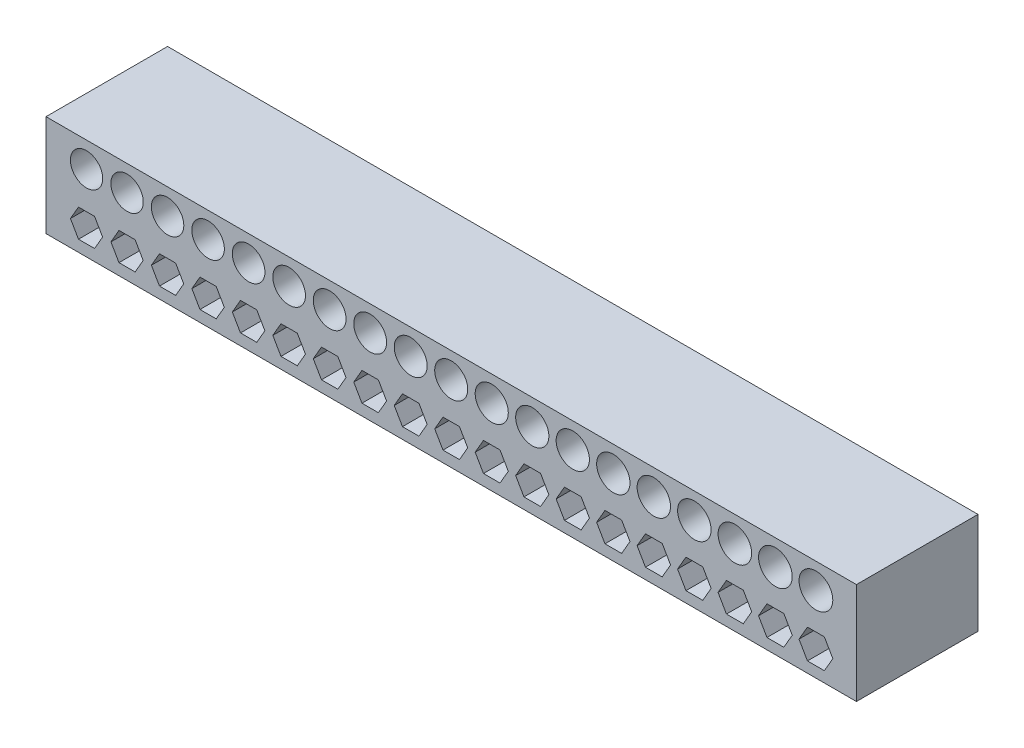
SolidWorks part; units mm, degrees
ref_plane "Front Plane" through (0, 0, 0) normal (0, 0, 1) x (1, 0, 0)
ref_plane "Top Plane" through (0, 0, 0) normal (0, 1, 0) x (1, 0, 0)
ref_plane "Right Plane" through (0, 0, 0) normal (1, 0, 0) x (0, 0, -1)
sketch "Sketch1" plane through (0, 0, 0) normal (0, 0, 1) x (1, 0, 0)
  line L0 (-93.9567, 6.25) -> (-91.9783, 9.6766) construction
  line L1 (-100, -12.5) -> (100, -12.5)
  line L2 (-100, -12.5) -> (-100, 12.5)
  line L3 (-100, 12.5) -> (100, 12.5)
  line L4 (100, -12.5) -> (100, 12.5)
  line L5 (-100, -12.5) -> (100, 12.5) construction
  line L6 (0, 12.5) -> (0, 0)
  line L7 (-91.9783, 9.6766) -> (-88.0217, 9.6766) construction
  line L8 (-88.0217, 9.6766) -> (-86.0433, 6.25) construction
  line L9 (-88.0217, 2.8234) -> (-91.9783, 2.8234) construction
  line L10 (-86.0433, 6.25) -> (-88.0217, 2.8234) construction
  line L11 (-91.9783, 2.8234) -> (-93.9567, 6.25) construction
  line L12 (-93.9567, 6.25) -> (-91.9783, 9.6766) construction
  line L13 (-91.9783, 9.6766) -> (-88.0217, 9.6766) construction
  line L14 (-88.0217, 9.6766) -> (-86.0433, 6.25) construction
  line L15 (-88.0217, 2.8234) -> (-91.9783, 2.8234) construction
  line L16 (-86.0433, 6.25) -> (-88.0217, 2.8234) construction
  line L17 (-91.9783, 2.8234) -> (-93.9567, 6.25) construction
  line L18 (0, 0) -> (0, -12.5)
  line L25 (-3.9567, -6.25) -> (-1.9783, -2.8234) construction
  line L26 (-13.9567, -6.25) -> (-11.9783, -2.8234) construction
  line L27 (-1.9783, -2.8234) -> (1.9783, -2.8234) construction
  line L28 (1.9783, -2.8234) -> (3.9567, -6.25) construction
  line L29 (1.9783, -9.6766) -> (-1.9783, -9.6766) construction
  line L30 (3.9567, -6.25) -> (1.9783, -9.6766) construction
  line L31 (-1.9783, -9.6766) -> (-3.9567, -6.25) construction
  line L32 (-1.9783, -9.6766) -> (1.9783, -2.8234) construction
  line L33 (-3.9567, -6.25) -> (3.9567, -6.25) construction
  line L34 (1.9783, -9.6766) -> (-1.9783, -2.8234) construction
  line L35 (-11.9783, -2.8234) -> (-8.0217, -2.8234) construction
  line L36 (-8.0217, -2.8234) -> (-6.0433, -6.25) construction
  line L37 (-6.0433, -6.25) -> (-8.0217, -9.6766) construction
  line L38 (-11.9783, -9.6766) -> (-13.9567, -6.25) construction
  line L39 (-8.0217, -9.6766) -> (-11.9783, -9.6766) construction
  line L40 (-23.9567, -6.25) -> (-21.9783, -2.8234) construction
  line L41 (-21.9783, -2.8234) -> (-18.0217, -2.8234) construction
  line L42 (-18.0217, -2.8234) -> (-16.0433, -6.25) construction
  line L43 (-16.0433, -6.25) -> (-18.0217, -9.6766) construction
  line L44 (-21.9783, -9.6766) -> (-23.9567, -6.25) construction
  line L45 (-18.0217, -9.6766) -> (-21.9783, -9.6766) construction
  line L46 (-33.9567, -6.25) -> (-31.9783, -2.8234) construction
  line L47 (-31.9783, -2.8234) -> (-28.0217, -2.8234) construction
  line L48 (-28.0217, -2.8234) -> (-26.0433, -6.25) construction
  line L49 (-26.0433, -6.25) -> (-28.0217, -9.6766) construction
  line L50 (-31.9783, -9.6766) -> (-33.9567, -6.25) construction
  line L51 (-28.0217, -9.6766) -> (-31.9783, -9.6766) construction
  line L52 (-43.9567, -6.25) -> (-41.9783, -2.8234) construction
  line L53 (-41.9783, -2.8234) -> (-38.0217, -2.8234) construction
  line L54 (-38.0217, -2.8234) -> (-36.0433, -6.25) construction
  line L55 (-36.0433, -6.25) -> (-38.0217, -9.6766) construction
  line L56 (-41.9783, -9.6766) -> (-43.9567, -6.25) construction
  line L57 (-38.0217, -9.6766) -> (-41.9783, -9.6766) construction
  line L58 (-53.9567, -6.25) -> (-51.9783, -2.8234) construction
  line L59 (-51.9783, -2.8234) -> (-48.0217, -2.8234) construction
  line L60 (-48.0217, -2.8234) -> (-46.0433, -6.25) construction
  line L61 (-46.0433, -6.25) -> (-48.0217, -9.6766) construction
  line L62 (-51.9783, -9.6766) -> (-53.9567, -6.25) construction
  line L63 (-48.0217, -9.6766) -> (-51.9783, -9.6766) construction
  line L64 (-63.9567, -6.25) -> (-61.9783, -2.8234) construction
  line L65 (-61.9783, -2.8234) -> (-58.0217, -2.8234) construction
  line L66 (-58.0217, -2.8234) -> (-56.0433, -6.25) construction
  line L67 (-56.0433, -6.25) -> (-58.0217, -9.6766) construction
  line L68 (-61.9783, -9.6766) -> (-63.9567, -6.25) construction
  line L69 (-58.0217, -9.6766) -> (-61.9783, -9.6766) construction
  line L70 (-73.9567, -6.25) -> (-71.9783, -2.8234) construction
  line L71 (-71.9783, -2.8234) -> (-68.0217, -2.8234) construction
  line L72 (-68.0217, -2.8234) -> (-66.0433, -6.25) construction
  line L73 (-66.0433, -6.25) -> (-68.0217, -9.6766) construction
  line L74 (-71.9783, -9.6766) -> (-73.9567, -6.25) construction
  line L75 (-68.0217, -9.6766) -> (-71.9783, -9.6766) construction
  line L76 (-83.9567, -6.25) -> (-81.9783, -2.8234) construction
  line L77 (-81.9783, -2.8234) -> (-78.0217, -2.8234) construction
  line L78 (-78.0217, -2.8234) -> (-76.0433, -6.25) construction
  line L79 (-76.0433, -6.25) -> (-78.0217, -9.6766) construction
  line L80 (-81.9783, -9.6766) -> (-83.9567, -6.25) construction
  line L81 (-78.0217, -9.6766) -> (-81.9783, -9.6766) construction
  line L82 (-93.9567, -6.25) -> (-91.9783, -2.8234) construction
  line L83 (-91.9783, -2.8234) -> (-88.0217, -2.8234) construction
  line L84 (-88.0217, -2.8234) -> (-86.0433, -6.25) construction
  line L85 (-86.0433, -6.25) -> (-88.0217, -9.6766) construction
  line L86 (-91.9783, -9.6766) -> (-93.9567, -6.25) construction
  line L87 (-88.0217, -9.6766) -> (-91.9783, -9.6766) construction
  line L88 (-3.9567, -6.25) -> (-13.9567, -6.25) construction
  line L89 (-91.9841, -2.8134) -> (-88.0159, -2.8134)
  line L90 (-88.0159, -2.8134) -> (-86.0318, -6.25)
  line L91 (-86.0318, -6.25) -> (-88.0159, -9.6866)
  line L92 (-88.0159, -9.6866) -> (-91.9841, -9.6866)
  line L93 (-91.9841, -9.6866) -> (-93.9682, -6.25)
  line L94 (-93.9682, -6.25) -> (-91.9841, -2.8134)
  line L95 (-81.9899, -2.8034) -> (-78.0101, -2.8034)
  line L96 (-78.0101, -2.8034) -> (-76.0202, -6.25)
  line L97 (-76.0202, -6.25) -> (-78.0101, -9.6966)
  line L98 (-78.0101, -9.6966) -> (-81.9899, -9.6966)
  line L99 (-81.9899, -9.6966) -> (-83.9798, -6.25)
  line L100 (-83.9798, -6.25) -> (-81.9899, -2.8034)
  line L101 (-71.9957, -2.7934) -> (-68.0043, -2.7934)
  line L102 (-68.0043, -2.7934) -> (-66.0087, -6.25)
  line L103 (-66.0087, -6.25) -> (-68.0043, -9.7066)
  line L104 (-68.0043, -9.7066) -> (-71.9957, -9.7066)
  line L105 (-71.9957, -9.7066) -> (-73.9913, -6.25)
  line L106 (-73.9913, -6.25) -> (-71.9957, -2.7934)
  line L107 (-62.0014, -2.7834) -> (-57.9986, -2.7834)
  line L108 (-57.9986, -2.7834) -> (-55.9971, -6.25)
  line L109 (-55.9971, -6.25) -> (-57.9986, -9.7166)
  line L110 (-57.9986, -9.7166) -> (-62.0014, -9.7166)
  line L111 (-62.0014, -9.7166) -> (-64.0029, -6.25)
  line L112 (-64.0029, -6.25) -> (-62.0014, -2.7834)
  line L113 (-52.0072, -2.7734) -> (-47.9928, -2.7734)
  line L114 (-47.9928, -2.7734) -> (-45.9856, -6.25)
  line L115 (-45.9856, -6.25) -> (-47.9928, -9.7266)
  line L116 (-47.9928, -9.7266) -> (-52.0072, -9.7266)
  line L117 (-52.0072, -9.7266) -> (-54.0144, -6.25)
  line L118 (-54.0144, -6.25) -> (-52.0072, -2.7734)
  line L119 (-42.013, -2.7634) -> (-37.987, -2.7634)
  line L120 (-37.987, -2.7634) -> (-35.974, -6.25)
  line L121 (-35.974, -6.25) -> (-37.987, -9.7366)
  line L122 (-37.987, -9.7366) -> (-42.013, -9.7366)
  line L123 (-42.013, -9.7366) -> (-44.026, -6.25)
  line L124 (-44.026, -6.25) -> (-42.013, -2.7634)
  line L125 (-32.0188, -2.7534) -> (-27.9812, -2.7534)
  line L126 (-27.9812, -2.7534) -> (-25.9625, -6.25)
  line L127 (-25.9625, -6.25) -> (-27.9812, -9.7466)
  line L128 (-27.9812, -9.7466) -> (-32.0188, -9.7466)
  line L129 (-32.0188, -9.7466) -> (-34.0375, -6.25)
  line L130 (-34.0375, -6.25) -> (-32.0188, -2.7534)
  line L131 (-22.0245, -2.7434) -> (-17.9755, -2.7434)
  line L132 (-17.9755, -2.7434) -> (-15.9509, -6.25)
  line L133 (-15.9509, -6.25) -> (-17.9755, -9.7566)
  line L134 (-17.9755, -9.7566) -> (-22.0245, -9.7566)
  line L135 (-22.0245, -9.7566) -> (-24.0491, -6.25)
  line L136 (-24.0491, -6.25) -> (-22.0245, -2.7434)
  line L137 (-12.0303, -2.7334) -> (-7.9697, -2.7334)
  line L138 (-7.9697, -2.7334) -> (-5.9394, -6.25)
  line L139 (-5.9394, -6.25) -> (-7.9697, -9.7666)
  line L140 (-7.9697, -9.7666) -> (-12.0303, -9.7666)
  line L141 (-12.0303, -9.7666) -> (-14.0606, -6.25)
  line L142 (-14.0606, -6.25) -> (-12.0303, -2.7334)
  line L143 (8.0217, -2.8234) -> (11.9783, -2.8234) construction
  line L144 (11.9783, -2.8234) -> (13.9567, -6.25) construction
  line L145 (13.9567, -6.25) -> (11.9783, -9.6766) construction
  line L146 (11.9783, -9.6766) -> (8.0217, -9.6766) construction
  line L147 (8.0217, -9.6766) -> (6.0433, -6.25) construction
  line L148 (6.0433, -6.25) -> (8.0217, -2.8234) construction
  line L149 (18.0217, -2.8234) -> (21.9783, -2.8234) construction
  line L150 (21.9783, -2.8234) -> (23.9567, -6.25) construction
  line L151 (23.9567, -6.25) -> (21.9783, -9.6766) construction
  line L152 (21.9783, -9.6766) -> (18.0217, -9.6766) construction
  line L153 (18.0217, -9.6766) -> (16.0433, -6.25) construction
  line L154 (16.0433, -6.25) -> (18.0217, -2.8234) construction
  line L155 (28.0217, -2.8234) -> (31.9783, -2.8234) construction
  line L156 (31.9783, -2.8234) -> (33.9567, -6.25) construction
  line L157 (33.9567, -6.25) -> (31.9783, -9.6766) construction
  line L158 (31.9783, -9.6766) -> (28.0217, -9.6766) construction
  line L159 (28.0217, -9.6766) -> (26.0433, -6.25) construction
  line L160 (26.0433, -6.25) -> (28.0217, -2.8234) construction
  line L161 (38.0217, -2.8234) -> (41.9783, -2.8234) construction
  line L162 (41.9783, -2.8234) -> (43.9567, -6.25) construction
  line L163 (43.9567, -6.25) -> (41.9783, -9.6766) construction
  line L164 (41.9783, -9.6766) -> (38.0217, -9.6766) construction
  line L165 (38.0217, -9.6766) -> (36.0433, -6.25) construction
  line L166 (36.0433, -6.25) -> (38.0217, -2.8234) construction
  line L167 (48.0217, -2.8234) -> (51.9783, -2.8234) construction
  line L168 (51.9783, -2.8234) -> (53.9567, -6.25) construction
  line L169 (53.9567, -6.25) -> (51.9783, -9.6766) construction
  line L170 (51.9783, -9.6766) -> (48.0217, -9.6766) construction
  line L171 (48.0217, -9.6766) -> (46.0433, -6.25) construction
  line L172 (46.0433, -6.25) -> (48.0217, -2.8234) construction
  line L173 (58.0217, -2.8234) -> (61.9783, -2.8234) construction
  line L174 (61.9783, -2.8234) -> (63.9567, -6.25) construction
  line L175 (63.9567, -6.25) -> (61.9783, -9.6766) construction
  line L176 (61.9783, -9.6766) -> (58.0217, -9.6766) construction
  line L177 (58.0217, -9.6766) -> (56.0433, -6.25) construction
  line L178 (56.0433, -6.25) -> (58.0217, -2.8234) construction
  line L179 (68.0217, -2.8234) -> (71.9783, -2.8234) construction
  line L180 (71.9783, -2.8234) -> (73.9567, -6.25) construction
  line L181 (73.9567, -6.25) -> (71.9783, -9.6766) construction
  line L182 (71.9783, -9.6766) -> (68.0217, -9.6766) construction
  line L183 (68.0217, -9.6766) -> (66.0433, -6.25) construction
  line L184 (66.0433, -6.25) -> (68.0217, -2.8234) construction
  line L185 (78.0217, -2.8234) -> (81.9783, -2.8234) construction
  line L186 (81.9783, -2.8234) -> (83.9567, -6.25) construction
  line L187 (83.9567, -6.25) -> (81.9783, -9.6766) construction
  line L188 (81.9783, -9.6766) -> (78.0217, -9.6766) construction
  line L189 (78.0217, -9.6766) -> (76.0433, -6.25) construction
  line L190 (76.0433, -6.25) -> (78.0217, -2.8234) construction
  line L191 (88.0217, -2.8234) -> (91.9783, -2.8234) construction
  line L192 (91.9783, -2.8234) -> (93.9567, -6.25) construction
  line L193 (93.9567, -6.25) -> (91.9783, -9.6766) construction
  line L194 (91.9783, -9.6766) -> (88.0217, -9.6766) construction
  line L195 (88.0217, -9.6766) -> (86.0433, -6.25) construction
  line L196 (86.0433, -6.25) -> (88.0217, -2.8234) construction
  line L197 (-2.0361, -2.7234) -> (2.0361, -2.7234)
  line L198 (2.0361, -2.7234) -> (4.0722, -6.25)
  line L199 (4.0722, -6.25) -> (2.0361, -9.7766)
  line L200 (2.0361, -9.7766) -> (-2.0361, -9.7766)
  line L201 (-2.0361, -9.7766) -> (-4.0722, -6.25)
  line L202 (-4.0722, -6.25) -> (-2.0361, -2.7234)
  line L203 (7.9581, -2.7134) -> (12.0419, -2.7134)
  line L204 (12.0419, -2.7134) -> (14.0837, -6.25)
  line L205 (14.0837, -6.25) -> (12.0419, -9.7866)
  line L206 (12.0419, -9.7866) -> (7.9581, -9.7866)
  line L207 (7.9581, -9.7866) -> (5.9163, -6.25)
  line L208 (5.9163, -6.25) -> (7.9581, -2.7134)
  line L209 (17.9524, -2.7034) -> (22.0476, -2.7034)
  line L210 (22.0476, -2.7034) -> (24.0953, -6.25)
  line L211 (24.0953, -6.25) -> (22.0476, -9.7966)
  line L212 (22.0476, -9.7966) -> (17.9524, -9.7966)
  line L213 (17.9524, -9.7966) -> (15.9047, -6.25)
  line L214 (15.9047, -6.25) -> (17.9524, -2.7034)
  line L215 (27.9466, -2.6934) -> (32.0534, -2.6934)
  line L216 (32.0534, -2.6934) -> (34.1068, -6.25)
  line L217 (34.1068, -6.25) -> (32.0534, -9.8066)
  line L218 (32.0534, -9.8066) -> (27.9466, -9.8066)
  line L219 (27.9466, -9.8066) -> (25.8932, -6.25)
  line L220 (25.8932, -6.25) -> (27.9466, -2.6934)
  line L221 (37.9408, -2.6834) -> (42.0592, -2.6834)
  line L222 (42.0592, -2.6834) -> (44.1184, -6.25)
  line L223 (44.1184, -6.25) -> (42.0592, -9.8166)
  line L224 (42.0592, -9.8166) -> (37.9408, -9.8166)
  line L225 (37.9408, -9.8166) -> (35.8816, -6.25)
  line L226 (35.8816, -6.25) -> (37.9408, -2.6834)
  line L227 (47.935, -2.6734) -> (52.065, -2.6734)
  line L228 (52.065, -2.6734) -> (54.1299, -6.25)
  line L229 (54.1299, -6.25) -> (52.065, -9.8266)
  line L230 (52.065, -9.8266) -> (47.935, -9.8266)
  line L231 (47.935, -9.8266) -> (45.8701, -6.25)
  line L232 (45.8701, -6.25) -> (47.935, -2.6734)
  line L233 (57.9293, -2.6634) -> (62.0707, -2.6634)
  line L234 (62.0707, -2.6634) -> (64.1415, -6.25)
  line L235 (64.1415, -6.25) -> (62.0707, -9.8366)
  line L236 (62.0707, -9.8366) -> (57.9293, -9.8366)
  line L237 (57.9293, -9.8366) -> (55.8585, -6.25)
  line L238 (55.8585, -6.25) -> (57.9293, -2.6634)
  line L239 (67.9235, -2.6534) -> (72.0765, -2.6534)
  line L240 (72.0765, -2.6534) -> (74.153, -6.25)
  line L241 (74.153, -6.25) -> (72.0765, -9.8466)
  line L242 (72.0765, -9.8466) -> (67.9235, -9.8466)
  line L243 (67.9235, -9.8466) -> (65.847, -6.25)
  line L244 (65.847, -6.25) -> (67.9235, -2.6534)
  line L245 (77.9177, -2.6434) -> (82.0823, -2.6434)
  line L246 (82.0823, -2.6434) -> (84.1645, -6.25)
  line L247 (84.1645, -6.25) -> (82.0823, -9.8566)
  line L248 (82.0823, -9.8566) -> (77.9177, -9.8566)
  line L249 (77.9177, -9.8566) -> (75.8355, -6.25)
  line L250 (75.8355, -6.25) -> (77.9177, -2.6434)
  line L251 (87.912, -2.6334) -> (92.088, -2.6334)
  line L252 (92.088, -2.6334) -> (94.1761, -6.25)
  line L253 (94.1761, -6.25) -> (92.088, -9.8666)
  line L254 (92.088, -9.8666) -> (87.912, -9.8666)
  line L255 (87.912, -9.8666) -> (85.8239, -6.25)
  line L256 (85.8239, -6.25) -> (87.912, -2.6334)
  circle A0 centre (-90, 6.25) radius 3.975 construction
  circle A1 centre (-90, 6.25) radius 3.975 construction
  circle A2 centre (0, 6.25) radius 3.975 construction
  circle A3 centre (-10, 6.25) radius 3.975 construction
  circle A4 centre (-20, 6.25) radius 3.975 construction
  circle A5 centre (-30, 6.25) radius 3.975 construction
  circle A6 centre (-40, 6.25) radius 3.975 construction
  circle A7 centre (-50, 6.25) radius 3.975 construction
  circle A8 centre (-60, 6.25) radius 3.975 construction
  circle A9 centre (-70, 6.25) radius 3.975 construction
  circle A10 centre (-80, 6.25) radius 3.975 construction
  circle A11 centre (-90, 6.25) radius 3.975 construction
  circle A12 centre (-90, 6.25) radius 3.985
  circle A13 centre (-80, 6.25) radius 3.995
  circle A14 centre (-70, 6.25) radius 4.005
  circle A15 centre (-60, 6.25) radius 4.015
  circle A16 centre (-50, 6.25) radius 4.025
  circle A17 centre (-40, 6.25) radius 4.035
  circle A18 centre (-30, 6.25) radius 4.045
  circle A19 centre (-20, 6.25) radius 4.055
  circle A20 centre (-10, 6.25) radius 4.065
  circle A21 centre (10, 6.25) radius 3.975 construction
  circle A22 centre (20, 6.25) radius 3.975 construction
  circle A23 centre (30, 6.25) radius 3.975 construction
  circle A24 centre (40, 6.25) radius 3.975 construction
  circle A25 centre (50, 6.25) radius 3.975 construction
  circle A26 centre (60, 6.25) radius 3.975 construction
  circle A27 centre (70, 6.25) radius 3.975 construction
  circle A28 centre (80, 6.25) radius 3.975 construction
  circle A29 centre (90, 6.25) radius 3.975 construction
  circle A30 centre (0, 6.25) radius 4.075
  circle A31 centre (10, 6.25) radius 4.085
  circle A32 centre (20, 6.25) radius 4.095
  circle A33 centre (30, 6.25) radius 4.105
  circle A34 centre (40, 6.25) radius 4.115
  circle A35 centre (50, 6.25) radius 4.125
  circle A36 centre (60, 6.25) radius 4.135
  circle A37 centre (70, 6.25) radius 4.145
  circle A38 centre (80, 6.25) radius 4.155
  circle A39 centre (90, 6.25) radius 4.165
  point P0 (0, 0)
  point P17 (0, 0)
  point P26 (0, -6.25)
  point P27 (0, -6.25)
  point P28 (0, -6.25)
  dimension "D2" = 200
  dimension "D1" = 25
  dimension "D4" = 10
  dimension "D5" = 0.01
  dimension "D6" = 0.02
  dimension "D7" = 0.03
  dimension "D8" = 0.04
  dimension "D9" = 0.05
  dimension "D10" = 0.06
  dimension "D11" = 0.07
  dimension "D12" = 0.08
  dimension "D13" = 0.09
  dimension "D15" = 0.1
  dimension "D16" = 0.11
  dimension "D17" = 0.12
  dimension "D18" = 0.13
  dimension "D19" = 0.14
  dimension "D20" = 0.15
  dimension "D21" = 0.16
  dimension "D22" = 0.17
  dimension "D23" = 0.18
  dimension "D24" = 0.19
  dimension "D3" = 10
  dimension "D14" = 10
extrude "Boss-Extrude1" add sketch "Sketch1" against normal blind 30 contours L18 L6 L3 L2 L1 A14 A13 A12 L93 L94 L89 L90 L91 L92 L99 L100 L95 L96 L97 L98 L105 L106 L101 L102 L103 L104 | L6 L18 L1 L4 L3 region at (-51.6064, -0.3314, 0) region at (51.2706, -0.3451, 0)
equation "\"tolerance_test_step\" = 0.01mm"
equation "\"D5@Sketch1\"=\"tolerance_test_step\""
equation "\"D6@Sketch1\"=\"tolerance_test_step\"*2"
equation "\"D7@Sketch1\"=\"tolerance_test_step\"*3"
equation "\"D8@Sketch1\"=\"tolerance_test_step\"*4"
equation "\"D9@Sketch1\"=\"tolerance_test_step\"*5"
equation "\"D10@Sketch1\"=\"tolerance_test_step\"*6"
equation "\"D11@Sketch1\"=\"tolerance_test_step\"*7"
equation "\"D12@Sketch1\"=\"tolerance_test_step\"*8"
equation "\"D13@Sketch1\"=\"tolerance_test_step\"*9"
equation "\"D15@Sketch1\"=\"tolerance_test_step\"*10"
equation "\"D16@Sketch1\"=\"tolerance_test_step\"*11"
equation "\"D17@Sketch1\"=\"tolerance_test_step\"*12"
equation "\"D18@Sketch1\"=\"tolerance_test_step\"*13"
equation "\"D19@Sketch1\"=\"tolerance_test_step\"*14"
equation "\"D20@Sketch1\"=\"tolerance_test_step\"*15"
equation "\"D21@Sketch1\"=\"tolerance_test_step\"*16"
equation "\"D22@Sketch1\"=\"tolerance_test_step\"*17"
equation "\"D23@Sketch1\"=\"tolerance_test_step\"*18"
equation "\"D24@Sketch1\"=\"tolerance_test_step\"*19"
